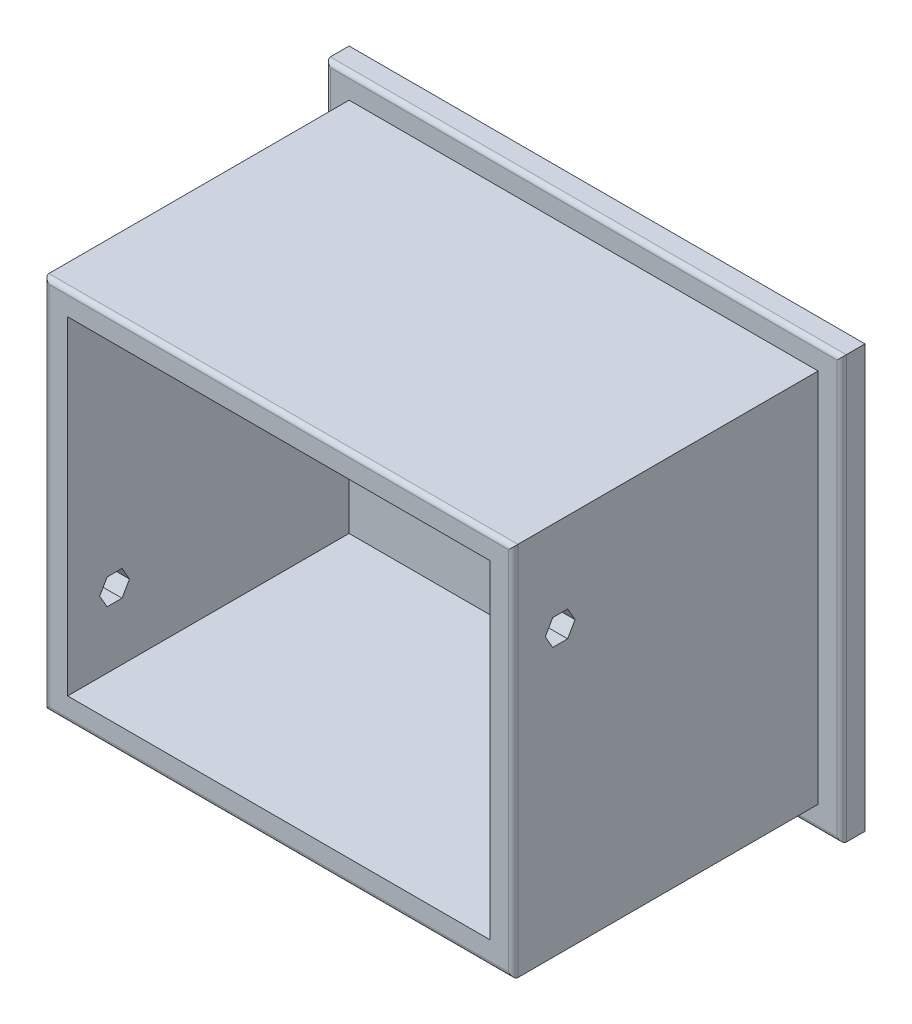
SolidWorks part; units mm, degrees
ref_plane "Plan de face" through (0, 0, 0) normal (0, 0, 1) x (1, 0, 0)
ref_plane "Plan de dessus" through (0, 0, 0) normal (0, 1, 0) x (1, 0, 0)
ref_plane "Plan de droite" through (0, 0, 0) normal (1, 0, 0) x (0, 0, -1)
sketch "Esquisse1" plane through (0, 0, 0) normal (0, 0, 1) x (1, 0, 0)
  line L0 (-192.776, 43.345) -> (-152.776, 47.845)
  line L1 (-152.776, 47.845) -> (115.224, 47.845)
  line L2 (-152.776, 47.845) -> (-152.776, -102.155)
  line L3 (-152.776, -102.155) -> (115.224, -102.155)
  line L4 (115.224, 47.845) -> (115.224, -102.155)
  line L5 (-152.776, 47.845) -> (-192.776, 47.845)
  line L6 (-152.776, 53.8314) -> (-152.776, -102.155)
  line L7 (-152.776, 47.845) -> (-152.776, -102.155)
  line L8 (-152.776, -102.155) -> (-192.776, -102.155)
  line L9 (-192.776, 47.845) -> (-192.776, -102.155)
  line L10 (-152.776, 47.845) -> (-192.776, 47.845)
  line L11 (-152.776, 47.845) -> (-152.776, 43.345)
  line L12 (-152.776, 43.345) -> (-192.776, 43.345)
  line L13 (-192.776, 47.845) -> (-192.776, 43.345)
  line L14 (-152.776, -102.155) -> (-192.776, -102.155)
  line L15 (-152.776, -102.155) -> (-152.776, -97.655)
  line L16 (-152.776, -97.655) -> (-192.776, -97.655)
  line L17 (-192.776, -102.155) -> (-192.776, -97.655)
  line L18 (-192.776, -97.655) -> (-152.776, -102.155)
  line L20 (-103.377, -67.155) -> (-3.377, -67.155)
  line L21 (-103.377, -67.155) -> (-103.377, 12.845)
  line L22 (-103.377, 12.845) -> (-3.377, 12.845)
  line L23 (-3.377, -67.155) -> (-3.377, 12.845)
  line L24 (-144.9874, 47.845) -> (-124.9874, 47.845)
  line L25 (-144.9874, 47.845) -> (-144.9874, 45.845)
  line L26 (-144.9874, 45.845) -> (-124.9874, 45.845)
  line L27 (-124.9874, 47.845) -> (-124.9874, 45.845)
  line L28 (-144.9874, -102.155) -> (-124.9874, -102.155)
  line L29 (-144.9874, -102.155) -> (-144.9874, -100.155)
  line L30 (-144.9874, -100.155) -> (-124.9874, -100.155)
  line L31 (-124.9874, -102.155) -> (-124.9874, -100.155)
  line L32 (-108.377, -72.155) -> (1.623, -72.155)
  line L33 (-108.377, -72.155) -> (-108.377, 17.845)
  line L34 (-108.377, 17.845) -> (1.623, 17.845)
  line L35 (1.623, -72.155) -> (1.623, 17.845)
  line L36 (-98.377, 7.845) -> (-8.377, 7.845)
  line L37 (-98.377, 7.845) -> (-98.377, -62.155)
  line L38 (-98.377, -62.155) -> (-8.377, -62.155)
  line L39 (-8.377, 7.845) -> (-8.377, -62.155)
  arc A0 (115.224, -102.155) -> (115.224, 47.845) centre (-162.1791, -27.155) ccw
  arc A1 (-192.776, -97.655) -> (-192.776, 43.345) centre (-63.7022, -27.155) cw
  circle A2 centre (-215.776, -27.155) radius 2.5
  circle A3 centre (130.224, -27.155) radius 2.5
  circle A4 centre (-33.549, -107.155) radius 2.5
  circle A5 centre (-33.549, 52.845) radius 2.5
  point P11 (-210.776, -27.155)
  point P12 (125.224, -27.155)
  point P35 (-53.377, 17.845)
  dimension "D10" = 30
  dimension "D19" = 5
  dimension "D1" = 268
  dimension "D2" = 150
  dimension "D3" = 40
  dimension "D4" = 4.5
  dimension "D5" = 4.5
  dimension "D6" = 18
  dimension "D7" = 75
  dimension "D8" = 10
  dimension "D9" = 75
  dimension "D11" = 80
  dimension "D12" = 35
  dimension "D13" = 48
  dimension "D14" = 2
  dimension "D15" = 20
  dimension "D16" = 20
  dimension "D17" = 2
  dimension "D18" = 48
  dimension "D20" = 30
  dimension "D21" = 5
  dimension "D22" = 5
  dimension "D23" = 5
  dimension "D24" = 35
  dimension "D25" = 100
  dimension "D26" = 5
  dimension "D27" = 5
  dimension "D28" = 5
  dimension "D29" = 5
  dimension "D30" = 5
  dimension "D31" = 5
extrude "Boss.-Extru.1" add sketch "Esquisse1" along normal blind 5 contours L32 L35 L34 L33 L23 L20 L21 L22 region at (-106.9558, -27.155, 0)
extrude "Boss.-Extru.2" add sketch "Esquisse1<32>" along normal blind 70 contours L20 L23 L22 L21 L36 L39 L38 L37 region at (-102.0964, -27.155, 0)
sketch "Esquisse1<32>" plane through (0, 0, 0) normal (0, 0, 1) x (1, 0, 0) same geometry as "Esquisse1"
extrude "Boss.-Extru.3" add sketch "Esquisse1<33>" along normal blind 10 contours L39 L36 L37 L38 region at (-53.377, -27.155, 0)
sketch "Esquisse1<33>" plane through (0, 0, 0) normal (0, 0, 1) x (1, 0, 0) same geometry as "Esquisse1"
sketch "Esquisse11" plane through (-3.377, 0, 0) normal (1, 0, 0) x (0, 0, -1)
  line L0 (-70, 12.845) -> (-5, 12.845) construction
  line L1 (-56.8246, -7.155) -> (-58.4123, -4.405)
  line L2 (-58.4123, -4.405) -> (-61.5877, -4.405)
  line L3 (-61.5877, -4.405) -> (-63.1754, -7.155)
  line L4 (-63.1754, -7.155) -> (-61.5877, -9.905)
  line L5 (-61.5877, -9.905) -> (-58.4123, -9.905)
  line L6 (-58.4123, -9.905) -> (-56.8246, -7.155)
  line L8 (-70, -67.155) -> (-70, 12.845) construction
  circle A0 centre (-60, -7.155) radius 2.75 construction
  dimension "D1" = 5.5
  dimension "D2" = 20
  dimension "D3" = 10
extrude "Enlèv. mat.-Extru.3" cut sketch "Esquisse11" against normal blind 10
sketch "Esquisse13" plane through (-103.377, 0, 0) normal (-1, 0, 0) x (0, 0, 1)
  line L0 (70, -67.155) -> (70, 12.845) construction
  line L1 (63.1754, -47.155) -> (61.5877, -44.405)
  line L2 (61.5877, -44.405) -> (58.4123, -44.405)
  line L3 (58.4123, -44.405) -> (56.8246, -47.155)
  line L4 (56.8246, -47.155) -> (58.4123, -49.905)
  line L5 (58.4123, -49.905) -> (61.5877, -49.905)
  line L6 (61.5877, -49.905) -> (63.1754, -47.155)
  line L8 (70, -67.155) -> (5, -67.155) construction
  circle A0 centre (60, -47.155) radius 2.75 construction
  dimension "D1" = 5.5
  dimension "D2" = 10
  dimension "D3" = 20
extrude "Enlèv. mat.-Extru.4" cut sketch "Esquisse13" against normal blind 10
fillet "Congé1" radius 1 4 edges at (-53.377, -67.155, 70) (-3.377, -27.155, 70) (-53.377, 12.845, 70) (-103.377, -27.155, 70)
fillet "Congé2" radius 1 4 edges at (1.623, -27.155, 5) (-53.377, 17.845, 5) (-108.377, -27.155, 5) (-53.377, -72.155, 5)
sketch "Esquisse14" plane through (0, 0, 0) normal (0, 0, -1) x (-1, 0, 0)
